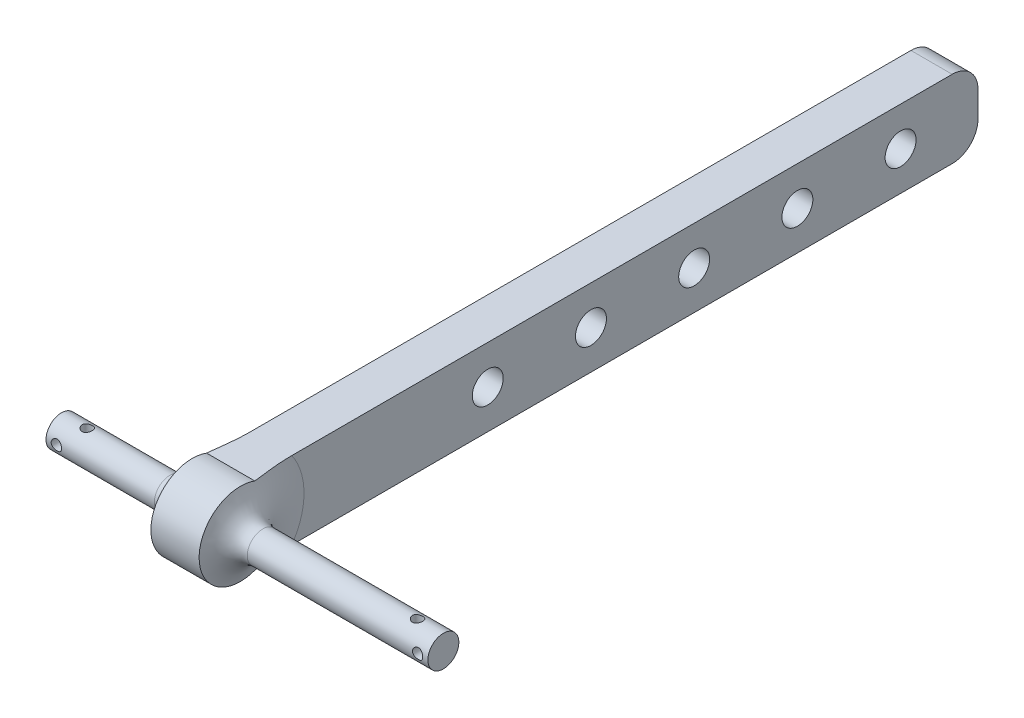
SolidWorks part; units mm, degrees
ref_plane "前视基准面" through (0, 0, 0) normal (0, 0, 1) x (1, 0, 0)
ref_plane "上视基准面" through (0, 0, 0) normal (0, 1, 0) x (1, 0, 0)
ref_plane "右视基准面" through (0, 0, 0) normal (1, 0, 0) x (0, 0, -1)
other "Configuration Table"
sketch "草图1" plane through (0, 0, 0) normal (1, 0, 0) x (0, 0, -1)
  line L1 (0, 0) -> (150, 0)
  line L2 (0, 0) -> (0, 15)
  line L3 (0, 15) -> (150, 15)
  line L4 (150, 0) -> (150, 15)
  dimension "D1" = 15
  dimension "D2" = 150
extrude "凸台-拉伸1" add sketch "草图1" along normal blind 8
fillet "圆角1" radius 5 4 edges at (4, 0, -150) (4, 15, -150) (4, 0, 0) (4, 15, 0)
sketch "草图6" plane through (8, 0, 0) normal (1, 0, 0) x (0, 0, -1)
  circle A0 centre (6.4, 7.5) radius 8
  dimension "D1" = 16
extrude "凸台-拉伸2" add sketch "草图6" against normal up to surface (8 mm away) up to face at (0, 7.5, -75)
sketch "草图15" plane through (0, 0, 0) normal (-1, 0, 0) x (0, 0, 1)
  circle A2 centre (-6.4, 7.5) radius 3
  dimension "D1" = 6
extrude "凸台-拉伸5" add sketch "草图15" along normal blind 26 and the other way blind 48
sketch "草图16" plane through (0, 0, 0) normal (0, 0, 1) x (1, 0, 0)
  line L0 (-26, 7.5) -> (-24.7951, 7.5) construction
  line L1 (-26, 10.5) -> (-26, 4.5) construction
  line L2 (48, 7.5) -> (28.4852, 7.5) construction
  line L3 (48, 4.5) -> (48, 10.5) construction
  circle A0 centre (-24, 7.5) radius 1
  circle A1 centre (46, 7.5) radius 1
  dimension "D2" = 2
  dimension "D3" = 2
  dimension "D1" = 2
  dimension "D4" = 2
extrude "切除-拉伸9" cut sketch "草图16" against normal up to next
sketch "草图17" plane through (0, 0, 0) normal (-1, 0, 0) x (0, 0, 1)
  line L0 (-150, 7.5) -> (-31.7081, 7.5) construction
  line L1 (-150, 5) -> (-150, 10) construction
  circle A0 centre (-135, 7.5) radius 3
  circle A1 centre (-115, 7.5) radius 3
  circle A2 centre (-95, 7.5) radius 3
  circle A3 centre (-75, 7.5) radius 3
  circle A4 centre (-55, 7.5) radius 3
  dimension "D6" = 6
  dimension "D7" = 6
  dimension "D8" = 6
  dimension "D9" = 6
  dimension "D10" = 6
  dimension "D1" = 15
  dimension "D2" = 20
  dimension "D3" = 20
  dimension "D4" = 20
  dimension "D5" = 20
extrude "切除-拉伸10" cut sketch "草图17" against normal up to next
sketch "草图18" plane through (0, 0, 0) normal (0, 1, 0) x (1, 0, 0)
  line L0 (-26, 6.4) -> (-12.4483, 6.4) construction
  line L1 (-26, 9.4) -> (-26, 3.4) construction
  line L2 (48, 3.4) -> (48, 9.4) construction
  circle A0 centre (-21, 6.4) radius 1
  circle A1 centre (43, 6.4) radius 1
  dimension "D2" = 2
  dimension "D4" = 2
  dimension "D1" = 5
  dimension "D3" = 5
extrude "切除-拉伸11" cut sketch "草图18" along normal blind 15
fillet "圆角2" radius 10 1 edges at (0, 7.5, -3.4) second distance 5 first distance on face at (0, 7.5, -132)
fillet "圆角3" radius 5 1 edges at (8, 7.5, -3.4) second distance 10 first distance on face at (43.1709, 4.6664, -5.4147)
